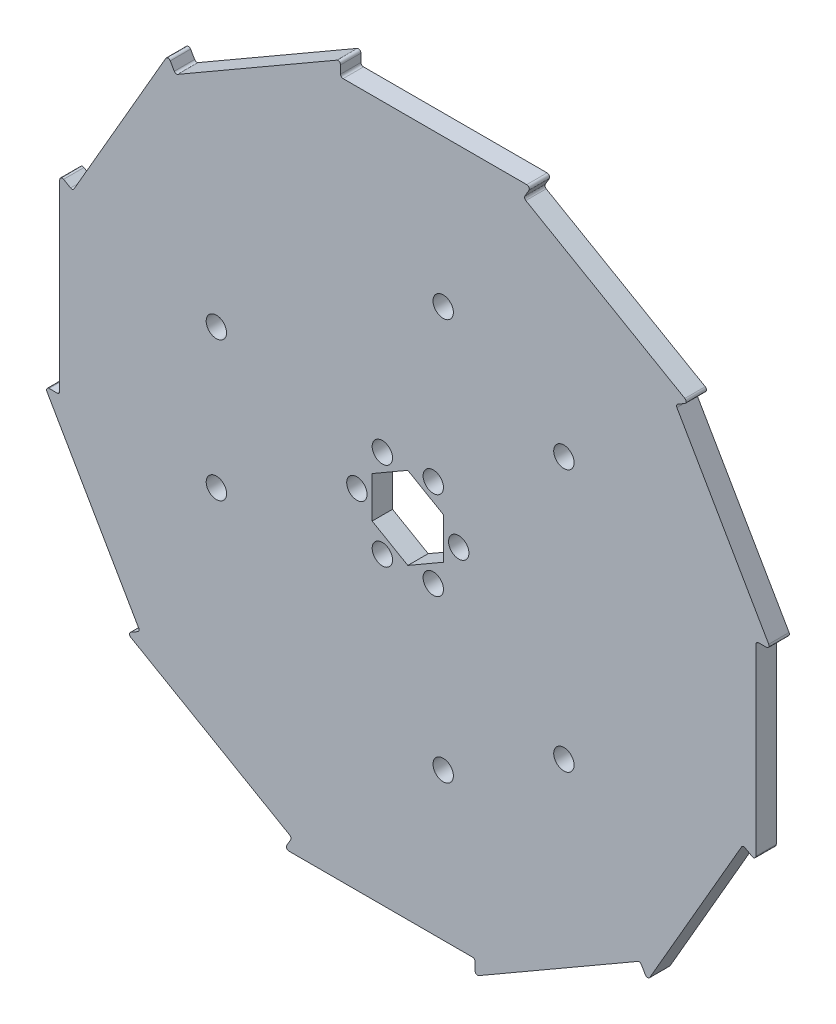
SolidWorks part; units mm, degrees
material "1023 Arkusz stali węglowej (SS)"
ref_plane "Front Plane" through (0, 0, 0) normal (0, 0, 1) x (1, 0, 0)
ref_plane "Top Plane" through (0, 0, 0) normal (0, 1, 0) x (1, 0, 0)
ref_plane "Right Plane" through (0, 0, 0) normal (1, 0, 0) x (0, 0, -1)
sketch "Sketch1" plane through (0, 0, 0) normal (0, 0, 1) x (1, 0, 0)
  line L0 (45.8501, -53.0147) -> (46.6425, -54.3872)
  line L1 (34.1686, -59.1817) -> (45.1671, -52.8317)
  line L2 (59.1817, -34.1686) -> (47.5085, -54.3872)
  line L3 (66.2147, -22.987) -> (67.5872, -23.7794)
  line L4 (59.1817, -34.1686) -> (65.5317, -23.1701)
  line L5 (68.3372, 0) -> (68.3372, -23.3464)
  line L6 (68.8372, 13.2) -> (70.4219, 13.2)
  line L7 (68.3372, 0) -> (68.3372, 12.7)
  line L8 (59.1817, 34.1686) -> (70.8549, 13.95)
  line L9 (53.0147, 45.8501) -> (54.3872, 46.6425)
  line L10 (59.1817, 34.1686) -> (52.8317, 45.1671)
  line L11 (34.1686, 59.1817) -> (54.3872, 47.5085)
  line L12 (-66.2147, 22.987) -> (-67.5872, 23.7794)
  line L13 (-59.1817, 34.1686) -> (-65.5317, 23.1701)
  line L14 (-68.3372, 0) -> (-68.3372, 23.3464)
  line L15 (-68.8372, -13.2) -> (-70.4219, -13.2)
  line L16 (-68.3372, 0) -> (-68.3372, -12.7)
  line L17 (-59.1817, -34.1686) -> (-70.8549, -13.95)
  line L18 (-53.0147, -45.8501) -> (-54.3872, -46.6425)
  line L19 (-59.1817, -34.1686) -> (-52.8317, -45.1671)
  line L20 (-34.1686, -59.1817) -> (-54.3872, -47.5085)
  line L21 (-45.8501, 53.0147) -> (-46.6425, 54.3872)
  line L22 (-34.1686, 59.1817) -> (-45.1671, 52.8317)
  line L23 (-59.1817, 34.1686) -> (-47.5085, 54.3872)
  line L24 (22.987, 66.2147) -> (23.7794, 67.5872)
  line L25 (34.1686, 59.1817) -> (23.1701, 65.5317)
  line L26 (0, 68.3372) -> (23.3464, 68.3372)
  line L27 (-13.2, 68.8372) -> (-13.2, 70.4219)
  line L28 (0, 68.3372) -> (-12.7, 68.3372)
  line L29 (-34.1686, 59.1817) -> (-13.95, 70.8549)
  line L30 (13.2, -68.8372) -> (13.2, -70.4219)
  line L31 (0, -68.3372) -> (12.7, -68.3372)
  line L32 (34.1686, -59.1817) -> (13.95, -70.8549)
  line L33 (-22.987, -66.2147) -> (-23.7794, -67.5872)
  line L34 (-34.1686, -59.1817) -> (-23.1701, -65.5317)
  line L35 (0, -68.3372) -> (-23.3464, -68.3372)
  line L36 (0, 8.0829) -> (7, 4.0415)
  line L37 (-7, -4.0415) -> (-7, 4.0415)
  line L38 (0, -8.0829) -> (-7, -4.0415)
  line L39 (-7, 4.0415) -> (0, 8.0829)
  line L40 (7, -4.0415) -> (0, -8.0829)
  line L41 (7, 4.0415) -> (7, -4.0415)
  arc A0 (46.6425, -54.3872) -> (47.5085, -54.3872) centre (47.0755, -54.1372) ccw
  arc A1 (45.8501, -53.0147) -> (45.1671, -52.8317) centre (45.4171, -53.2647) ccw
  arc A2 (67.5872, -23.7794) -> (68.3372, -23.3464) centre (67.8372, -23.3464) ccw
  arc A3 (66.2147, -22.987) -> (65.5317, -23.1701) centre (65.9647, -23.4201) ccw
  arc A4 (70.4219, 13.2) -> (70.8549, 13.95) centre (70.4219, 13.7) ccw
  arc A5 (68.8372, 13.2) -> (68.3372, 12.7) centre (68.8372, 12.7) ccw
  arc A6 (54.3872, 46.6425) -> (54.3872, 47.5085) centre (54.1372, 47.0755) ccw
  arc A7 (53.0147, 45.8501) -> (52.8317, 45.1671) centre (53.2647, 45.4171) ccw
  arc A8 (-67.5872, 23.7794) -> (-68.3372, 23.3464) centre (-67.8372, 23.3464) ccw
  arc A9 (-66.2147, 22.987) -> (-65.5317, 23.1701) centre (-65.9647, 23.4201) ccw
  arc A10 (-70.4219, -13.2) -> (-70.8549, -13.95) centre (-70.4219, -13.7) ccw
  arc A11 (-68.8372, -13.2) -> (-68.3372, -12.7) centre (-68.8372, -12.7) ccw
  arc A12 (-54.3872, -46.6425) -> (-54.3872, -47.5085) centre (-54.1372, -47.0755) ccw
  arc A13 (-53.0147, -45.8501) -> (-52.8317, -45.1671) centre (-53.2647, -45.4171) ccw
  arc A14 (-46.6425, 54.3872) -> (-47.5085, 54.3872) centre (-47.0755, 54.1372) ccw
  arc A15 (-45.8501, 53.0147) -> (-45.1671, 52.8317) centre (-45.4171, 53.2647) ccw
  arc A16 (23.7794, 67.5872) -> (23.3464, 68.3372) centre (23.3464, 67.8372) ccw
  arc A17 (22.987, 66.2147) -> (23.1701, 65.5317) centre (23.4201, 65.9647) ccw
  arc A18 (-13.2, 70.4219) -> (-13.95, 70.8549) centre (-13.7, 70.4219) ccw
  arc A19 (-13.2, 68.8372) -> (-12.7, 68.3372) centre (-12.7, 68.8372) ccw
  arc A20 (13.2, -70.4219) -> (13.95, -70.8549) centre (13.7, -70.4219) ccw
  arc A21 (13.2, -68.8372) -> (12.7, -68.3372) centre (12.7, -68.8372) ccw
  arc A22 (-23.7794, -67.5872) -> (-23.3464, -68.3372) centre (-23.3464, -67.8372) ccw
  arc A23 (-22.987, -66.2147) -> (-23.1701, -65.5317) centre (-23.4201, -65.9647) ccw
  circle A24 centre (-37.5877, 13.6808) radius 2
  circle A25 centre (30.6418, 25.7115) radius 2
  circle A26 centre (-37.5877, -13.6808) radius 2
  circle A27 centre (6.9459, -39.3923) radius 2
  circle A28 centre (30.6418, -25.7115) radius 2
  circle A29 centre (6.9459, 39.3923) radius 2
  circle A30 centre (5, 8.6603) radius 2
  circle A31 centre (-10, 0) radius 2
  circle A32 centre (5, -8.6603) radius 2
  circle A33 centre (-5, 8.6603) radius 2
  circle A34 centre (-5, -8.6603) radius 2
  circle A35 centre (10, 0) radius 2
extrude "Boss-Extrude1" add sketch "Sketch1" along normal blind 4
